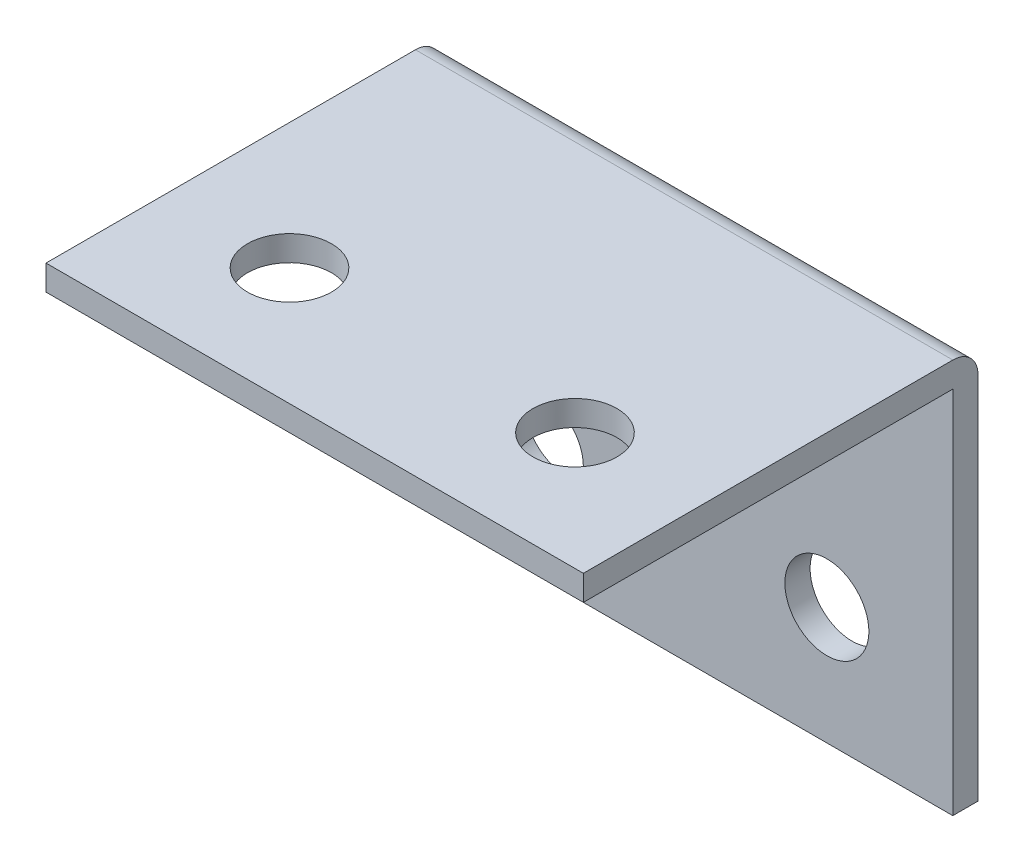
SolidWorks part; units mm, degrees
ref_plane "前视基准面" through (0, 0, 0) normal (0, 0, 1) x (1, 0, 0)
ref_plane "上视基准面" through (0, 0, 0) normal (0, 1, 0) x (1, 0, 0)
ref_plane "右视基准面" through (0, 0, 0) normal (1, 0, 0) x (0, 0, -1)
sketch "草图1" plane through (0, 0, 0) normal (0, 0, 1) x (1, 0, 0)
  line L1 (0, 0) -> (32, 0)
  line L2 (0, 0) -> (0, 23.5)
  line L3 (0, 23.5) -> (32, 23.5)
  line L4 (32, 0) -> (32, 23.5)
  dimension "D1" = 32
  dimension "D2" = 23.5
sketch "草图2" plane through (0, 0, 0) normal (0, 0, 1) x (1, 0, 0)
extrude "凸台-拉伸2" add sketch "草图1" along normal blind 23.5
shell "抽壳1" thickness 1.5 removed face at (32, 11.75, 11.75) removed face at (16, 11.75, 23.5) removed face at (0, 11.75, 11.75) removed face at (16, 0, 11.75)
fillet "圆角2" radius 1.5 1 edges at (16, 23.5, 0) type face fillet first side face at (16, 23.5, 11.75) second side face at (16, 11.75, 0)
sketch "草图3" plane through (0, 0, 1.5) normal (0, 0, 1) x (1, 0, 0)
  line L0 (16, 22) -> (16, 0) construction
  line L1 (32, 22) -> (0, 22) construction
  line L2 (0, 0) -> (32, 0) construction
  line L3 (-1.0524, 7) -> (33.1678, 7) construction
  circle A0 centre (7.5, 7) radius 2.5
  circle A1 centre (24.5, 7) radius 2.5
  dimension "D2" = 5
  dimension "D1" = 7
  dimension "D3" = 17
extrude "切除-拉伸2" cut sketch "草图3" against normal blind 23.5 contours A0 | A1
sketch "草图5" plane through (0, 22, 0) normal (0, -1, 0) x (1, 0, 0)
  line L0 (16, 23.5) -> (16, 2.1941) construction
  line L1 (32, 23.5) -> (0, 23.5) construction
  line L2 (0, 16.5) -> (32.6867, 16.5) construction
  line L3 (0, 23.5) -> (0, 1.5) construction
  circle A0 centre (7.5, 16.5) radius 2.5
  circle A1 centre (24.5, 16.5) radius 2.5
  dimension "D2" = 5
  dimension "D1" = 7
  dimension "D3" = 17
extrude "切除-拉伸3" cut sketch "草图5" against normal blind 23.5 contours A0 | A1
